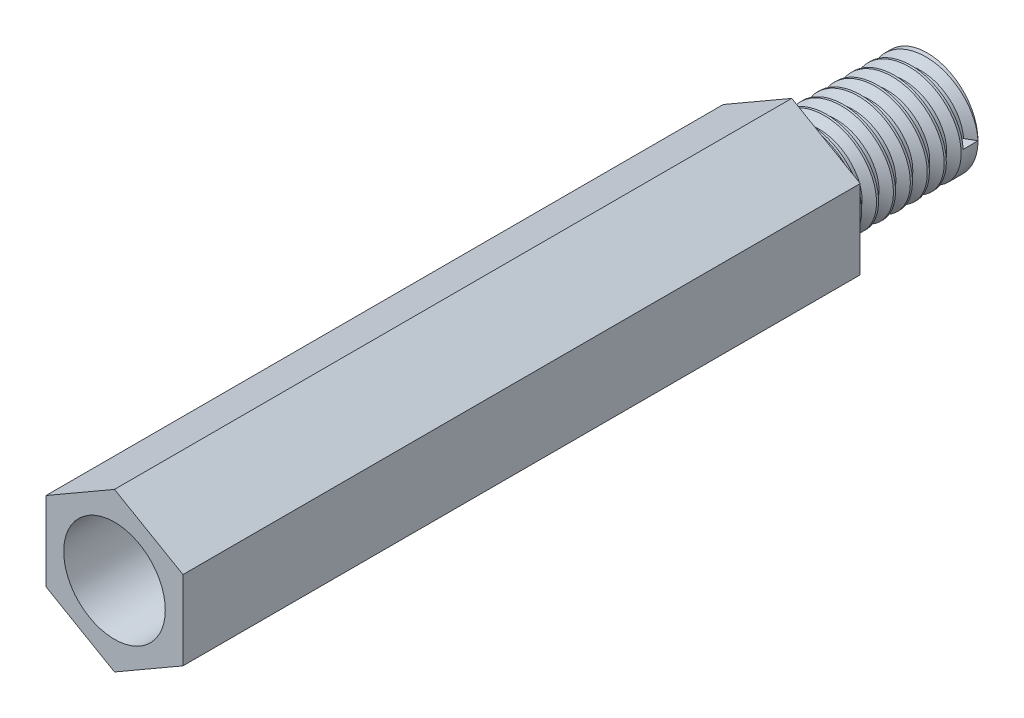
SolidWorks part; units mm, degrees
ref_plane "前视基准面" through (0, 0, 0) normal (0, 0, 1) x (1, 0, 0)
ref_plane "上视基准面" through (0, 0, 0) normal (0, 1, 0) x (1, 0, 0)
ref_plane "右视基准面" through (0, 0, 0) normal (1, 0, 0) x (0, 0, -1)
other "Configuration Table"
sketch "草图1" plane through (0, 0, 0) normal (0, 0, 1) x (1, 0, 0)
  circle A0 centre (0, 0) radius 1.5
  circle A1 centre (0, 0) radius 2.335
  dimension "D1" = 3
  dimension "D2" = 4.67
extrude "凸台-拉伸1" add sketch "草图1" along normal blind 20
sketch "草图3" plane through (0, 0, 0) normal (0, 0, 1) x (1, 0, 0)
  line L1 (0, 2.335) -> (-2.0222, 1.1675)
  line L2 (-2.0222, 1.1675) -> (-2.0222, -1.1675)
  line L3 (-2.0222, -1.1675) -> (0, -2.335)
  line L4 (0, -2.335) -> (2.0222, -1.1675)
  line L5 (2.0222, -1.1675) -> (2.0222, 1.1675)
  line L6 (2.0222, 1.1675) -> (0, 2.335)
  circle A0 centre (0, 0) radius 2.0222 construction
extrude "切除-拉伸2" cut sketch "草图3" along normal blind 20 flip side to cut
sketch "草图4" plane through (0, 0, 0) normal (0, 0, 1) x (1, 0, 0)
  circle A0 centre (0, 0) radius 1.5
extrude "凸台-拉伸2" add sketch "草图4" against normal blind 4 separate body
thread "螺纹线1" pitch 0.5 method cut profile "螺纹线轮廓1" start angle 0, offset 0, length 4, pitch 0.5, diameter 3
ref_plane "基准面1" through (1.5, 0, -4) normal (0, -1, 0) x (1, 0, 0)
sketch "螺纹线轮廓1" plane through (1.5, 0, -4) normal (0, -1, 0) x (1, 0, 0)
  line L0 (0, 0) -> (0, 0.5) construction
  line L11 (0, 0) -> (0, 0.4375)
  line L12 (0, 0.4375) -> (-0.2706, 0.2812)
  line L13 (-0.2706, 0.2812) -> (-0.2706, 0.1562)
  line L15 (-0.2706, 0.1562) -> (0, 0)
  line L17 (-0.2706, 0.2187) -> (0, 0.2187) construction
  point P2 (0, 0)
  dimension "Pitch" = 0.5
  dimension "Profile_Angle" = 60
  dimension "Profile_Land" = 0.125
  dimension "Profile_Height" = 0.2706
